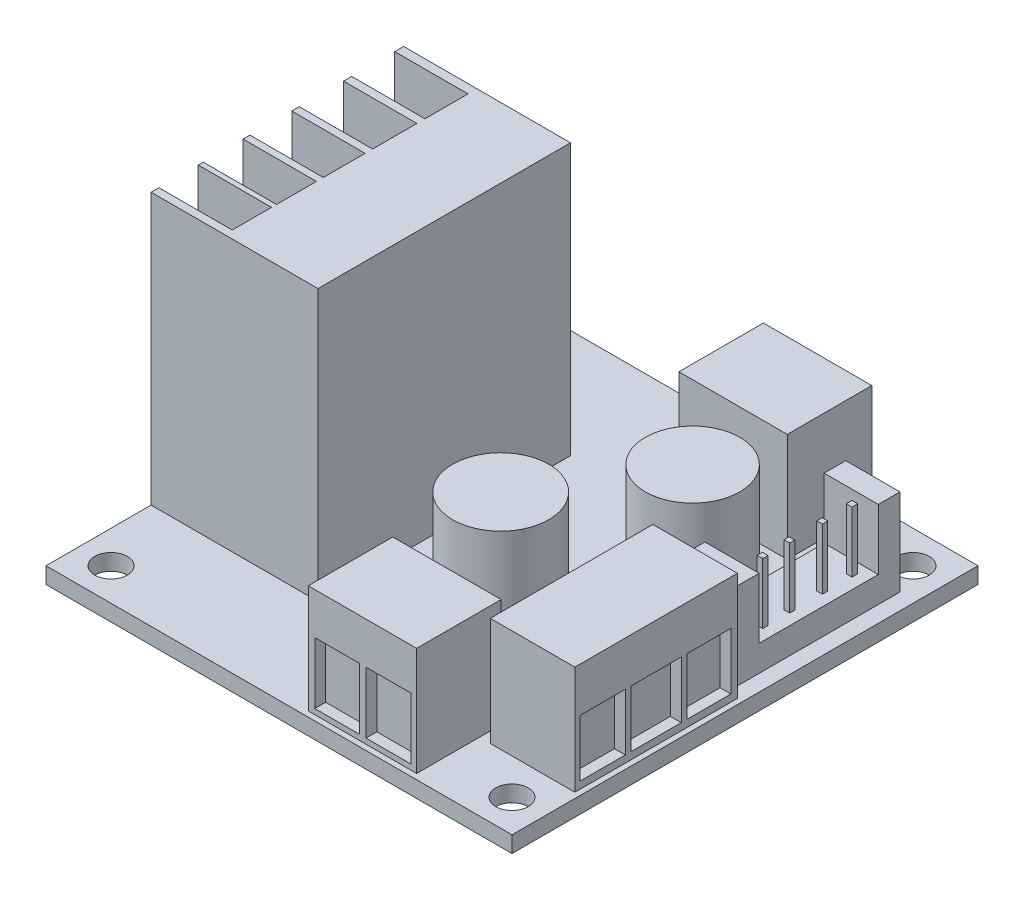
SolidWorks part; units mm, degrees
ref_plane "Front" through (0, 0, 0) normal (0, 0, 1) x (1, 0, 0)
ref_plane "Top" through (0, 0, 0) normal (0, 1, 0) x (1, 0, 0)
ref_plane "Right" through (0, 0, 0) normal (1, 0, 0) x (0, 0, -1)
sketch "草圖1" plane through (0, 0, 0) normal (0, 1, 0) x (1, 0, 0)
  line L1 (0, 0) -> (43, 0)
  line L2 (0, 0) -> (0, 43)
  line L3 (0, 43) -> (43, 43)
  line L4 (43, 0) -> (43, 43)
  dimension "D1" = 43
  dimension "D2" = 43
extrude "填料-伸長1" add sketch "草圖1" along normal blind 1.5
sketch "草圖2" plane through (0, 1.5, 0) normal (0, 1, 0) x (1, 0, 0)
  line L0 (43, 0) -> (43, 43) construction
  line L1 (34.7, 21.3) -> (42.5, 21.3)
  line L2 (34.7, 21.3) -> (34.7, 6.3)
  line L3 (34.7, 6.3) -> (42.5, 6.3)
  line L4 (42.5, 21.3) -> (42.5, 6.3)
  line L5 (23.7, 8.3) -> (33.7, 8.3)
  line L6 (23.7, 8.3) -> (23.7, 0.5)
  line L7 (23.7, 0.5) -> (33.7, 0.5)
  line L8 (33.7, 8.3) -> (33.7, 0.5)
  line L9 (23.7, 34.7) -> (33.7, 34.7)
  line L10 (23.7, 34.7) -> (23.7, 42.5)
  line L11 (23.7, 42.5) -> (33.7, 42.5)
  line L12 (33.7, 34.7) -> (33.7, 42.5)
  line L13 (0, 0) -> (43, 0) construction
  line L14 (43, 43) -> (0, 43) construction
  dimension "D1" = 15
  dimension "D2" = 7.8
  dimension "D3" = 7.8
  dimension "D4" = 10
  dimension "D5" = 10
  dimension "D6" = 7.8
  dimension "D7" = 0.5
  dimension "D8" = 6.3
  dimension "D9" = 9.3
  dimension "D10" = 0.5
  dimension "D11" = 0.5
  dimension "D12" = 9.3
extrude "填料-伸長2" add sketch "草圖2" along normal blind 10 separate body
sketch "草圖3" plane through (0, 1.5, 0) normal (0, 1, 0) x (1, 0, 0)
  line L0 (0, 43) -> (0, 0) construction
  line L1 (0, 9.7) -> (15.4, 9.7)
  line L2 (0, 9.7) -> (0, 33)
  line L3 (0, 33) -> (15.4, 33)
  line L4 (15.4, 9.7) -> (15.4, 33)
  line L5 (43, 43) -> (0, 43) construction
  dimension "D1" = 23.3
  dimension "D2" = 10
  dimension "D3" = 15.4
extrude "填料-伸長3" add sketch "草圖3" along normal blind 25 separate body
sketch "草圖4" plane through (0, 26.5, 0) normal (0, 1, 0) x (1, 0, 0)
  line L0 (0, 33) -> (0, 9.7) construction
  line L1 (0, 32.1773) -> (6.7647, 32.1773)
  line L2 (0, 32.1773) -> (0, 28.2057)
  line L3 (0, 28.2057) -> (6.7647, 28.2057)
  line L4 (6.7647, 32.1773) -> (6.7647, 28.2057)
  line L6 (0, 27.4574) -> (6.7647, 27.4574)
  line L7 (0, 27.4574) -> (0, 23.3707)
  line L8 (0, 23.3707) -> (6.7647, 23.3707)
  line L9 (6.7647, 27.4574) -> (6.7647, 23.3707)
  line L10 (0, 22.68) -> (6.7647, 22.68)
  line L11 (0, 22.68) -> (0, 18.8235)
  line L12 (0, 18.8235) -> (6.7647, 18.8235)
  line L13 (6.7647, 22.68) -> (6.7647, 18.8235)
  line L14 (0, 18.1903) -> (6.7647, 18.1903)
  line L15 (0, 18.1903) -> (0, 14.5065)
  line L16 (0, 14.5065) -> (6.7647, 14.5065)
  line L17 (6.7647, 18.1903) -> (6.7647, 14.5065)
  line L18 (0, 14.046) -> (6.7647, 14.046)
  line L19 (0, 14.046) -> (0, 10.4197)
  line L20 (0, 10.4197) -> (6.7647, 10.4197)
  line L21 (6.7647, 14.046) -> (6.7647, 10.4197)
extrude "除料-伸長1" cut sketch "草圖4" against normal blind 25
sketch "草圖5" plane through (0, 1.5, 0) normal (0, 1, 0) x (1, 0, 0)
  circle A0 centre (31.7447, 27.9154) radius 4.3594
  circle A1 centre (25.0807, 16.875) radius 4.4359
extrude "填料-伸長4" add sketch "草圖5" along normal blind 10 separate body
sketch "草圖6" plane through (42.5, 0, 0) normal (1, 0, 0) x (0, 0, -1)
  line L1 (6.7778, 7.4011) -> (10.9587, 7.4011)
  line L2 (6.7778, 7.4011) -> (6.7778, 2.1527)
  line L3 (6.7778, 2.1527) -> (10.9587, 2.1527)
  line L4 (10.9587, 7.4011) -> (10.9587, 2.1527)
  line L5 (11.4925, 7.4011) -> (16.1182, 7.4011)
  line L6 (11.4925, 7.4011) -> (11.4925, 2.1527)
  line L7 (11.4925, 2.1527) -> (16.1182, 2.1527)
  line L8 (16.1182, 7.4011) -> (16.1182, 2.1527)
  line L9 (16.6519, 7.4011) -> (20.6994, 7.4011)
  line L10 (16.6519, 7.4011) -> (16.6519, 2.1527)
  line L11 (16.6519, 2.1527) -> (20.6994, 2.1527)
  line L12 (20.6994, 7.4011) -> (20.6994, 2.1527)
extrude "除料-伸長2" cut sketch "草圖6" against normal blind 1
sketch "草圖8" plane through (0, 0, -0.5) normal (0, 0, 1) x (1, 0, 0)
  line L1 (24.306, 7.6619) -> (28.4119, 7.6619)
  line L2 (24.306, 7.6619) -> (24.306, 1.9934)
  line L3 (24.306, 1.9934) -> (28.4119, 1.9934)
  line L4 (28.4119, 7.6619) -> (28.4119, 1.9934)
  line L5 (29.0247, 7.6619) -> (33.1612, 7.6619)
  line L6 (29.0247, 7.6619) -> (29.0247, 1.9934)
  line L7 (29.0247, 1.9934) -> (33.1612, 1.9934)
  line L8 (33.1612, 7.6619) -> (33.1612, 1.9934)
extrude "除料-伸長3" cut sketch "草圖8" against normal blind 1
sketch "草圖9" plane through (0, 0, -42.5) normal (0, 0, -1) x (-1, 0, 0)
  line L1 (-32.9885, 7.7613) -> (-28.7889, 7.7613)
  line L2 (-32.9885, 7.7613) -> (-32.9885, 2.1263)
  line L3 (-32.9885, 2.1263) -> (-28.7889, 2.1263)
  line L4 (-28.7889, 7.7613) -> (-28.7889, 2.1263)
  line L5 (-28.0978, 7.7613) -> (-24.3234, 7.7613)
  line L6 (-28.0978, 7.7613) -> (-28.0978, 2.1263)
  line L7 (-28.0978, 2.1263) -> (-24.3234, 2.1263)
  line L8 (-24.3234, 7.7613) -> (-24.3234, 2.1263)
extrude "除料-伸長4" cut sketch "草圖9" against normal blind 1
sketch "草圖10" plane through (0, 0, 0) normal (0, -1, 0) x (1, 0, 0)
  line L0 (0, 0) -> (43, 0) construction
  line L1 (3, -3) -> (40, -3) construction
  line L2 (3, -3) -> (3, -40) construction
  line L3 (3, -40) -> (40, -40) construction
  line L4 (40, -3) -> (40, -40) construction
  line L5 (0, -43) -> (0, 0) construction
  circle A0 centre (40, -3) radius 1.5
  circle A1 centre (3, -3) radius 1.5
  circle A2 centre (3, -40) radius 1.5
  circle A3 centre (40, -40) radius 1.5
  dimension "D3" = 3
  dimension "D1" = 37
  dimension "D2" = 37
  dimension "D4" = 3
  dimension "D5" = 3
extrude "除料-伸長5" cut sketch "草圖10" against normal blind 3
sketch "草圖11" plane through (0, 1.5, 0) normal (0, 1, 0) x (1, 0, 0)
  line L0 (43, 0) -> (43, 43) construction
  line L1 (36.5, 37.3) -> (41.5, 37.3)
  line L2 (36.5, 37.3) -> (36.5, 22.3)
  line L3 (36.5, 22.3) -> (41.5, 22.3)
  line L4 (41.5, 37.3) -> (41.5, 22.3)
  line L6 (42.5, 21.3) -> (34.7, 21.3) construction
  dimension "D1" = 15
  dimension "D2" = 5
  dimension "D3" = 1.5
  dimension "D4" = 1
extrude "填料-伸長5" add sketch "草圖11" along normal blind 2.4 separate body
sketch "草圖12" plane through (0, 3.9, 0) normal (0, 1, 0) x (1, 0, 0)
  line L1 (36.5, 37.3) -> (41.5, 37.3)
  line L2 (36.5, 37.3) -> (36.5, 35.3)
  line L3 (36.5, 35.3) -> (41.5, 35.3)
  line L4 (41.5, 37.3) -> (41.5, 35.3)
  line L5 (41.5, 22.3) -> (41.5, 37.3) construction
  line L6 (36.5, 22.3) -> (41.5, 22.3)
  line L7 (36.5, 22.3) -> (36.5, 24.3)
  line L8 (36.5, 24.3) -> (41.5, 24.3)
  line L9 (41.5, 22.3) -> (41.5, 24.3)
  point P4 (36.5, 22.3)
  point P5 (41.5, 24.3)
  point P15 (41.5, 35.3)
  dimension "D1" = 2
  dimension "D2" = 2
extrude "填料-伸長6" add sketch "草圖12" along normal blind 5.6
sketch "草圖13" plane through (0, 3.9, 0) normal (0, 1, 0) x (1, 0, 0)
  line L1 (39.9705, 34.4078) -> (40.4907, 34.4078)
  line L2 (39.9705, 34.4078) -> (39.9705, 33.8875)
  line L3 (39.9705, 33.8875) -> (40.4907, 33.8875)
  line L4 (40.4907, 34.4078) -> (40.4907, 33.8875)
  line L5 (39.9705, 31.6423) -> (40.4907, 31.6423)
  line L6 (39.9705, 31.6423) -> (39.9705, 31.1495)
  line L7 (39.9705, 31.1495) -> (40.4907, 31.1495)
  line L8 (40.4907, 31.6423) -> (40.4907, 31.1495)
  line L9 (39.9705, 28.6031) -> (40.4907, 28.6031)
  line L10 (39.9705, 28.6031) -> (39.9705, 28.1376)
  line L11 (39.9705, 28.1376) -> (40.4907, 28.1376)
  line L12 (40.4907, 28.6031) -> (40.4907, 28.1376)
  line L13 (39.9705, 26.1388) -> (40.4907, 26.1388)
  line L14 (39.9705, 26.1388) -> (39.9705, 25.646)
  line L15 (39.9705, 25.646) -> (40.4907, 25.646)
  line L16 (40.4907, 26.1388) -> (40.4907, 25.646)
extrude "填料-伸長7" add sketch "草圖13" along normal blind 5.6
